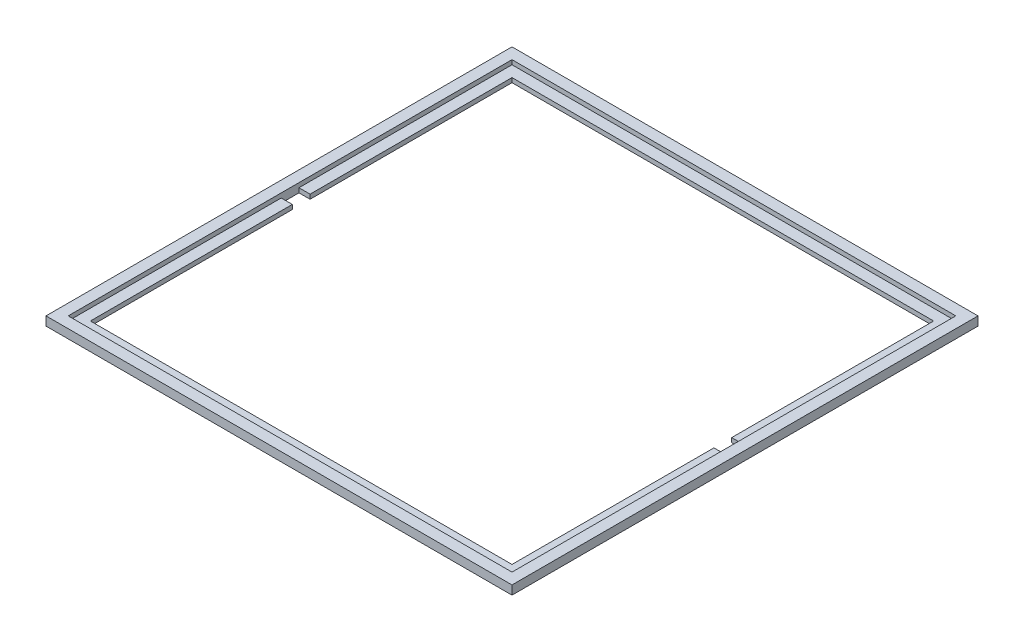
SolidWorks part; units mm, degrees
ref_plane "Front" through (0, 0, 0) normal (0, 0, 1) x (1, 0, 0)
ref_plane "Top" through (0, 0, 0) normal (0, 1, 0) x (1, 0, 0)
ref_plane "Right" through (0, 0, 0) normal (1, 0, 0) x (0, 0, -1)
sketch "Sketch1" plane through (0, 0, 0) normal (0, 1, 0) x (1, 0, 0)
  line L0 (-5, -5) -> (-5, 205)
  line L1 (0, 0) -> (200, 0)
  line L2 (0, 0) -> (0, 200)
  line L3 (0, 200) -> (200, 200)
  line L4 (200, 0) -> (200, 200)
  line L5 (-5, 205) -> (205, 205)
  line L6 (205, -5) -> (205, 205)
  line L7 (-5, -5) -> (205, -5)
  line L8 (5, 5) -> (195, 5)
  line L9 (195, 5) -> (195, 195)
  line L10 (5, 195) -> (195, 195)
  line L11 (5, 5) -> (5, 96)
  line L12 (2.5, 104) -> (2.5, 96) construction
  line L13 (0, 104) -> (5, 104)
  line L14 (0, 104) -> (0, 96)
  line L15 (0, 96) -> (5, 96)
  line L17 (5, 104) -> (5, 195)
  line L18 (5, 5) -> (5, 195) construction
  line L19 (100, 195) -> (100, 5) construction
  line L20 (197.5, 104) -> (197.5, 96) construction
  line L21 (200, 96) -> (195, 96)
  line L22 (200, 104) -> (200, 96)
  line L23 (200, 104) -> (195, 104)
  point P17 (195, 100)
  point P18 (0, 100)
  point P21 (2.5, 100)
  point P22 (200, 100)
  dimension "D1" = 200
  dimension "D4" = 8
  dimension "D2" = 5
  dimension "D3" = 5
extrude "Boss-Extrude1" add sketch "Sketch1" along normal blind 2 contours L0 L7 L6 L5 L4 L1 L2 L3 | L4 L21 L9 L8 L11 L15 L2 L1 | L23 L4 L3 L2 L13 L17 L10 L9 region at (-2.0302, 0, -100) region at (2.2185, 0, -48) region at (2.2185, 0, -152)
extrude "Boss-Extrude2" add sketch "Sketch1<4>" along normal blind 4 contours L0 L7 L6 L5 L4 L1 L2 L3 region at (-2.0302, 0, -100)
sketch "Sketch1<4>" plane through (0, 0, 0) normal (0, 1, 0) x (1, 0, 0) same geometry as "Sketch1"
